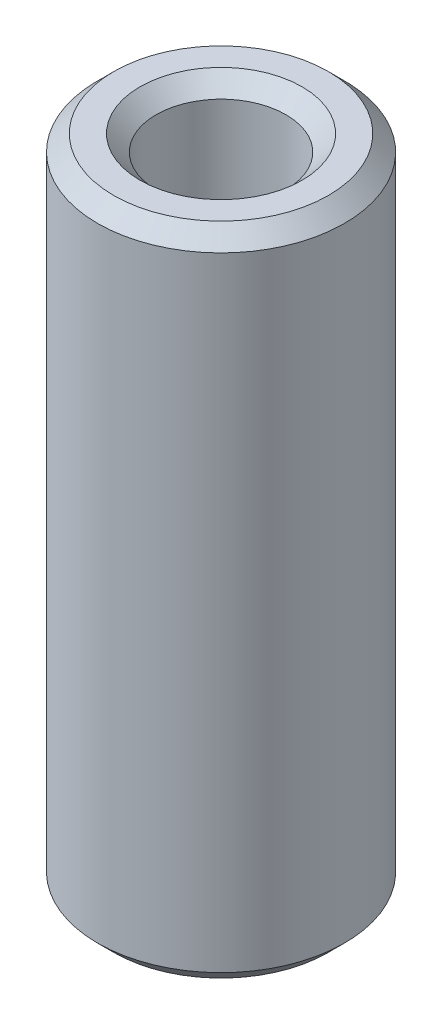
SolidWorks part; units mm, degrees
ref_plane "Front Plane" through (0, 0, 0) normal (0, 0, 1) x (1, 0, 0)
ref_plane "Top Plane" through (0, 0, 0) normal (0, 1, 0) x (1, 0, 0)
ref_plane "Right Plane" through (0, 0, 0) normal (1, 0, 0) x (0, 0, -1)
sketch "Sketch1" plane through (0, 0, 0) normal (0, 1, 0) x (1, 0, 0)
  circle A0 centre (0, 0) radius 20
  dimension "SLEEVE_OD" = 40
extrude "Boss-Extrude1" add sketch "Sketch1" along normal blind 106.1968
sketch "Sketch2" plane through (0, 0, 0) normal (0, 1, 0) x (1, 0, 0)
  circle A0 centre (0, 0) radius 10.5141
  dimension "BORE_D" = 21.0283
extrude "Cut-Extrude1" cut sketch "Sketch2" along normal through all
chamfer "Chamfer1" distance 2.6123 angle 45 4 edges at (0, 106.1968, 10.5141) (0, 0, 10.5141) (0, 0, 20) (0, 106.1968, 20)
